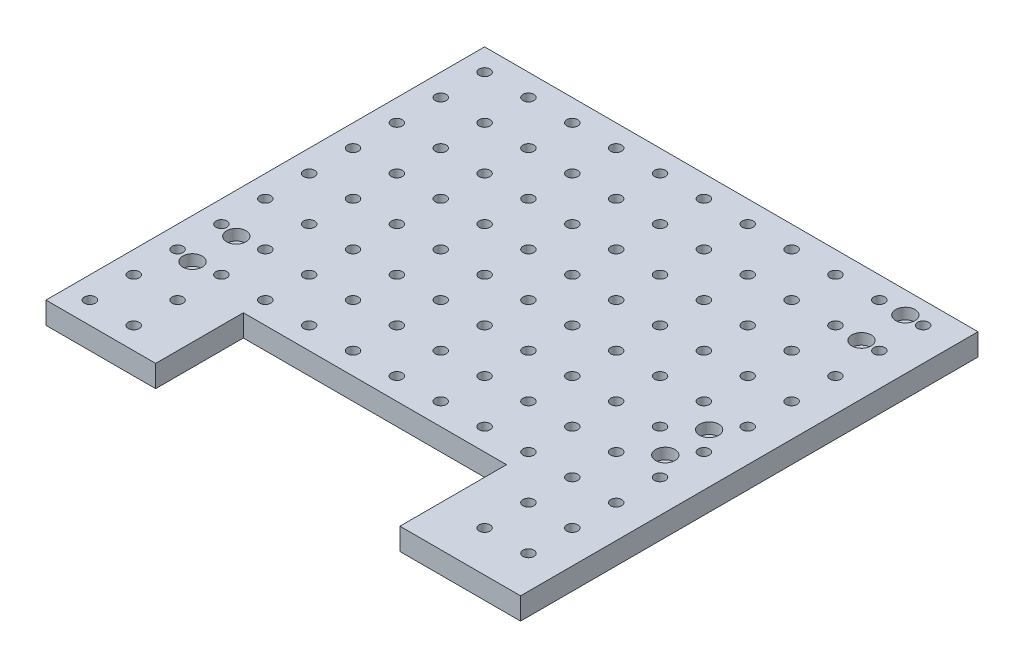
SolidWorks part; units mm, degrees
ref_plane "Front Plane" through (0, 0, 0) normal (0, 0, 1) x (1, 0, 0)
ref_plane "Top Plane" through (0, 0, 0) normal (0, 1, 0) x (1, 0, 0)
ref_plane "Right Plane" through (0, 0, 0) normal (1, 0, 0) x (0, 0, -1)
sketch "Sketch1" plane through (0, 0, 0) normal (0, 1, 0) x (1, 0, 0)
  line L1 (63.5, 0) -> (215.9, 0)
  line L2 (0, 0) -> (0, 203.2)
  line L3 (0, 203.2) -> (285.75, 203.2)
  line L4 (285.75, 0) -> (285.75, 203.2)
  line L6 (0, 0) -> (0, -50.8)
  line L7 (0, -50.8) -> (63.5, -50.8)
  line L8 (63.5, 0) -> (63.5, -50.8)
  line L10 (285.75, 0) -> (285.75, -61.722)
  line L11 (285.75, -61.722) -> (215.9, -61.722)
  line L12 (215.9, 0) -> (215.9, -61.722)
  circle A0 centre (12.7, 190.5) radius 3.175
  circle A1 centre (38.1, 190.5) radius 3.175
  circle A2 centre (63.5, 190.5) radius 3.175
  circle A3 centre (88.9, 190.5) radius 3.175
  circle A4 centre (114.3, 190.5) radius 3.175
  circle A5 centre (139.7, 190.5) radius 3.175
  circle A6 centre (165.1, 190.5) radius 3.175
  circle A7 centre (190.5, 190.5) radius 3.175
  circle A8 centre (215.9, 190.5) radius 3.175
  circle A9 centre (241.3, 190.5) radius 3.175
  circle A10 centre (266.7, 190.5) radius 3.175
  circle A11 centre (38.1, 165.1) radius 3.175
  circle A12 centre (63.5, 165.1) radius 3.175
  circle A13 centre (88.9, 165.1) radius 3.175
  circle A14 centre (114.3, 165.1) radius 3.175
  circle A15 centre (139.7, 165.1) radius 3.175
  circle A16 centre (165.1, 165.1) radius 3.175
  circle A17 centre (190.5, 165.1) radius 3.175
  circle A18 centre (215.9, 165.1) radius 3.175
  circle A19 centre (241.3, 165.1) radius 3.175
  circle A20 centre (266.7, 165.1) radius 3.175
  circle A21 centre (38.1, 139.7) radius 3.175
  circle A22 centre (63.5, 139.7) radius 3.175
  circle A23 centre (88.9, 139.7) radius 3.175
  circle A24 centre (114.3, 139.7) radius 3.175
  circle A25 centre (139.7, 139.7) radius 3.175
  circle A26 centre (165.1, 139.7) radius 3.175
  circle A27 centre (190.5, 139.7) radius 3.175
  circle A28 centre (215.9, 139.7) radius 3.175
  circle A29 centre (241.3, 139.7) radius 3.175
  circle A30 centre (266.7, 139.7) radius 3.175
  circle A31 centre (38.1, 114.3) radius 3.175
  circle A32 centre (63.5, 114.3) radius 3.175
  circle A33 centre (88.9, 114.3) radius 3.175
  circle A34 centre (114.3, 114.3) radius 3.175
  circle A35 centre (139.7, 114.3) radius 3.175
  circle A36 centre (165.1, 114.3) radius 3.175
  circle A37 centre (190.5, 114.3) radius 3.175
  circle A38 centre (215.9, 114.3) radius 3.175
  circle A39 centre (241.3, 114.3) radius 3.175
  circle A40 centre (266.7, 114.3) radius 3.175
  circle A41 centre (38.1, 88.9) radius 3.175
  circle A42 centre (63.5, 88.9) radius 3.175
  circle A43 centre (88.9, 88.9) radius 3.175
  circle A44 centre (114.3, 88.9) radius 3.175
  circle A45 centre (139.7, 88.9) radius 3.175
  circle A46 centre (165.1, 88.9) radius 3.175
  circle A47 centre (190.5, 88.9) radius 3.175
  circle A48 centre (215.9, 88.9) radius 3.175
  circle A49 centre (241.3, 88.9) radius 3.175
  circle A50 centre (266.7, 88.9) radius 3.175
  circle A51 centre (38.1, 63.5) radius 3.175
  circle A52 centre (63.5, 63.5) radius 3.175
  circle A53 centre (88.9, 63.5) radius 3.175
  circle A54 centre (114.3, 63.5) radius 3.175
  circle A55 centre (139.7, 63.5) radius 3.175
  circle A56 centre (165.1, 63.5) radius 3.175
  circle A57 centre (190.5, 63.5) radius 3.175
  circle A58 centre (215.9, 63.5) radius 3.175
  circle A59 centre (241.3, 63.5) radius 3.175
  circle A60 centre (266.7, 63.5) radius 3.175
  circle A61 centre (38.1, 38.1) radius 3.175
  circle A62 centre (63.5, 38.1) radius 3.175
  circle A63 centre (88.9, 38.1) radius 3.175
  circle A64 centre (114.3, 38.1) radius 3.175
  circle A65 centre (139.7, 38.1) radius 3.175
  circle A66 centre (165.1, 38.1) radius 3.175
  circle A67 centre (190.5, 38.1) radius 3.175
  circle A68 centre (215.9, 38.1) radius 3.175
  circle A69 centre (241.3, 38.1) radius 3.175
  circle A70 centre (266.7, 38.1) radius 3.175
  circle A71 centre (38.1, 12.7) radius 3.175
  circle A72 centre (63.5, 12.7) radius 3.175
  circle A73 centre (88.9, 12.7) radius 3.175
  circle A74 centre (114.3, 12.7) radius 3.175
  circle A75 centre (139.7, 12.7) radius 3.175
  circle A76 centre (165.1, 12.7) radius 3.175
  circle A77 centre (190.5, 12.7) radius 3.175
  circle A78 centre (215.9, 12.7) radius 3.175
  circle A79 centre (241.3, 12.7) radius 3.175
  circle A80 centre (266.7, 12.7) radius 3.175
  circle A81 centre (38.1, -12.7) radius 3.175
  circle A89 centre (241.3, -12.7) radius 3.175
  circle A90 centre (266.7, -12.7) radius 3.175
  circle A91 centre (38.1, -38.1) radius 3.175
  circle A99 centre (241.3, -38.1) radius 3.175
  circle A100 centre (266.7, -38.1) radius 3.175
  circle A101 centre (12.7, 165.1) radius 3.175
  circle A102 centre (12.7, 139.7) radius 3.175
  circle A103 centre (12.7, 114.3) radius 3.175
  circle A104 centre (12.7, 88.9) radius 3.175
  circle A105 centre (12.7, 63.5) radius 3.175
  circle A106 centre (12.7, 38.1) radius 3.175
  circle A107 centre (12.7, 12.7) radius 3.175
  circle A108 centre (12.7, -12.7) radius 3.175
  circle A109 centre (12.7, -38.1) radius 3.175
  circle A110 centre (88.9, -12.7) radius 3.175 [skipped]
  circle A111 centre (114.3, -12.7) radius 3.175 [skipped]
  circle A112 centre (139.7, -12.7) radius 3.175 [skipped]
  circle A113 centre (165.1, -12.7) radius 3.175 [skipped]
  circle A114 centre (190.5, -12.7) radius 3.175 [skipped]
  arc A115 (215.9, -15.875) -> (215.9, -9.525) centre (215.9, -12.7) ccw [skipped]
  arc A116 (215.9, -34.925) -> (215.9, -41.275) centre (215.9, -38.1) ccw [skipped]
  circle A117 centre (190.5, -38.1) radius 3.175 [skipped]
  circle A118 centre (165.1, -38.1) radius 3.175 [skipped]
  circle A119 centre (139.7, -38.1) radius 3.175 [skipped]
  circle A120 centre (114.3, -38.1) radius 3.175 [skipped]
  circle A121 centre (88.9, -38.1) radius 3.175 [skipped]
  arc A122 (63.5, -34.925) -> (63.5, -41.275) centre (63.5, -38.1) ccw [skipped]
  arc A123 (63.5, -9.525) -> (63.5, -15.875) centre (63.5, -12.7) ccw [skipped]
  dimension "D9" = 6.35
  dimension "D1" = 203.2
  dimension "D2" = 285.75
  dimension "D3" = 50.8
  dimension "D4" = 63.5
  dimension "D5" = 61.722
  dimension "D6" = 69.85
  dimension "D7" = 12.7
  dimension "D8" = 12.7
  dimension "D10" = 11
  dimension "D11" = 10
extrude "Boss-Extrude1" add sketch "Sketch1" along normal blind 12.7
sketch "Sketch2" plane through (0, 12.7, 0) normal (0, 1, 0) x (1, 0, 0)
  line L0 (285.75, -61.722) -> (285.75, 203.2) construction
  line L1 (285.75, 203.2) -> (0, 203.2) construction
  line L2 (0, 203.2) -> (0, -50.8) construction
  line L3 (0, -50.8) -> (63.5, -50.8) construction
  circle A0 centre (256.3717, 190.5) radius 3.429
  circle A1 centre (256.3717, 190.5) radius 5.588
  circle A2 centre (256.3717, 165.1) radius 3.429
  circle A3 centre (256.3717, 165.1) radius 5.588
  circle A4 centre (257.048, 76.2) radius 3.429
  circle A5 centre (257.048, 76.2) radius 5.588
  circle A6 centre (257.048, 50.8) radius 3.429
  circle A7 centre (257.048, 50.8) radius 5.588
  circle A8 centre (23.114, 10.922) radius 3.429
  circle A9 centre (23.114, 10.922) radius 5.588
  circle A10 centre (23.114, 36.322) radius 3.429
  circle A11 centre (23.114, 36.322) radius 5.588
  point P26 (0, 0)
  dimension "D1" = 11.176
  dimension "D2" = 6.858
  dimension "D8" = 6.858
  dimension "D9" = 11.176
  dimension "D3" = 25.4
  dimension "D4" = 25.4
  dimension "D5" = 28.702
  dimension "D6" = 88.9
  dimension "D7" = 127
  dimension "D10" = 23.114
  dimension "D11" = 25.4
  dimension "D12" = 61.722
extrude "Cut-Extrude1" cut sketch "Sketch2" against normal blind 12.7 contours A0 | A4 | A6 | A2
extrude "Cut-Extrude2" cut sketch "Sketch2<3>" against normal blind 6.35 contours A1 A0 | A3 A2 | A7 A6 | A5 A4 region at (250.9418, 12.7, -190.5) region at (250.9418, 12.7, -165.1) region at (251.6181, 12.7, -76.2) region at (251.6181, 12.7, -50.8)
sketch "Sketch2<3>" plane through (0, 12.7, 0) normal (0, 1, 0) x (1, 0, 0) same geometry as "Sketch2"
extrude "Cut-Extrude3" cut sketch "Sketch2<4>" against normal blind 12.7 contours A8 | A10 region at (23.114, 12.7, -10.922) region at (23.114, 12.7, -36.322)
sketch "Sketch2<4>" plane through (0, 12.7, 0) normal (0, 1, 0) x (1, 0, 0) same geometry as "Sketch2"
extrude "Cut-Extrude4" cut sketch "Sketch2<5>" against normal blind 6.35 contours A11 A10 | A9 A8 region at (17.6841, 12.7, -10.922) region at (17.6841, 12.7, -36.322)
sketch "Sketch2<5>" plane through (0, 12.7, 0) normal (0, 1, 0) x (1, 0, 0) same geometry as "Sketch2"
